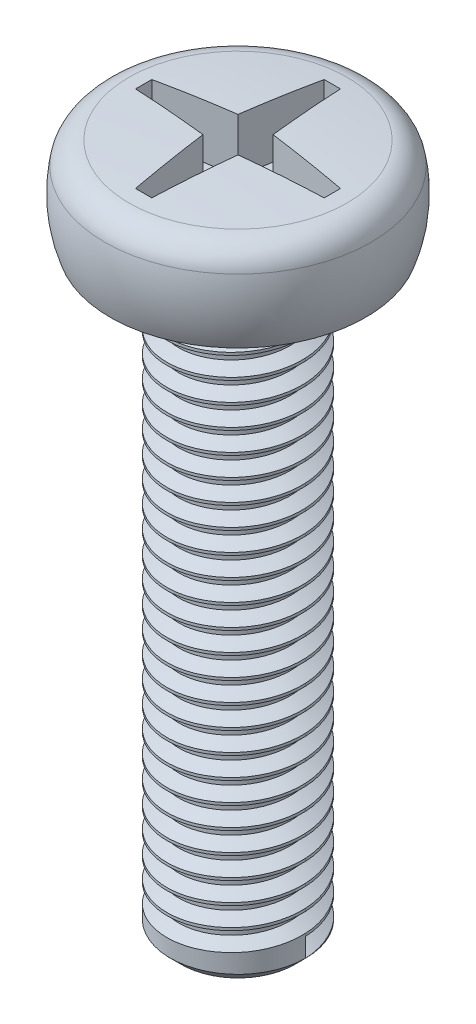
SolidWorks part; units mm, degrees
material "ASTM A36 Steel"
ref_plane "Front Plane" through (0, 0, 0) normal (0, 0, 1) x (1, 0, 0)
ref_plane "Top Plane" through (0, 0, 0) normal (0, 1, 0) x (1, 0, 0)
ref_plane "Right Plane" through (0, 0, 0) normal (1, 0, 0) x (0, 0, -1)
sketch "Sketch1" plane through (0, 0, 0) normal (0, 0, 1) x (1, 0, 0)
  line L0 (0, 3.2272) -> (0, -0.2728) construction
  line L1 (0, 3.2272) -> (5, 3.2272) construction
  line L2 (5, 3.2272) -> (5, -0.2728) construction
  line L3 (5, -0.2728) -> (0, -0.2728) construction
  line L4 (5, 1.4772) -> (0, 1.4772) construction
  line L5 (0, 2.9428) -> (4.7253, 2.9428) construction
  line L6 (4.7139, -0.2728) -> (0, -0.2728)
  line L7 (0, 3.2272) -> (0, -0.2728)
  arc A0 (4.7139, 2.9745) -> (0, 3.2272) centre (0, -40.8721) ccw
  arc A1 (4.7139, -0.2728) -> (4.7139, 2.9745) centre (0.2499, 1.3508) ccw
  point P11 (0, 1.4772)
  dimension "D1" = 3.5
  dimension "D2" = 5
revolve "Revolve1" add sketch "Sketch1" angle 360 about L7
fillet "Fillet1" radius 1 1 edges at (-4.7139, 2.9745, 0)
sketch "Sketch2" plane through (0, -0.2728, 0) normal (0, -1, 0) x (1, 0, 0)
  line L0 (0, 0) -> (0, -3.7135) construction
  line L1 (-0.3, -3.485) -> (0.3, -3.485)
  line L8 (0.3, -3.485) -> (0.6473, -0.6473)
  line L12 (-0.3, -3.485) -> (-0.6473, -0.6473)
  line L16 (-3.485, 0.3) -> (-3.485, -0.3)
  line L17 (-3.485, -0.3) -> (-0.6473, -0.6473)
  line L18 (-3.485, 0.3) -> (-0.6473, 0.6473)
  line L19 (0, 0) -> (-3.7135, 0) construction
  line L20 (0.3, 3.485) -> (-0.3, 3.485)
  line L21 (-0.3, 3.485) -> (-0.6473, 0.6473)
  line L22 (0.3, 3.485) -> (0.6473, 0.6473)
  line L23 (0, 0) -> (0, 3.7135) construction
  line L24 (3.485, -0.3) -> (3.485, 0.3)
  line L25 (3.485, 0.3) -> (0.6473, 0.6473)
  line L26 (3.485, -0.3) -> (0.6473, -0.6473)
  line L27 (0, 0) -> (3.7135, 0) construction
  point P6 (0, -3.485)
  point P15 (-3.485, 0)
  point P21 (0, 3.485)
  point P28 (3.485, 0)
  point P29 (0, 0)
  dimension "D1" = 0.3
  dimension "D2" = 4
extrude "Cut-Extrude1" cut sketch "Sketch2" along normal blind 2 from surface starting at face at (4.0261, 3.043, 0)
sketch "Sketch3" plane through (0, -0.2728, 0) normal (0, -1, 0) x (1, 0, 0)
  circle A0 centre (0, 0) radius 2.5
  dimension "D1" = 5
extrude "Boss-Extrude1" add sketch "Sketch3" along normal blind 22
chamfer "Chamfer1" distance 0.4 angle 45 1 edges at (2.5, -22.2728, 0)
thread "Thread1" pitch 0.8 start angle 0, offset 0, length 0, pitch 0.8, diameter 5
ref_plane "Plane1" through (2.5, -21.8728, 0) normal (0, 0, 1) x (1, 0, 0)
sketch "Thread Profile1" plane through (2.5, -21.8728, 0) normal (0, 0, 1) x (1, 0, 0)
  line L0 (0, 0) -> (0, 0.8) construction
  line L11 (0, 0) -> (0, 0.7)
  line L12 (0, 0.7) -> (-0.433, 0.45)
  line L13 (-0.433, 0.45) -> (-0.433, 0.25)
  line L15 (-0.433, 0.25) -> (0, 0)
  line L17 (-0.433, 0.35) -> (0, 0.35) construction
  point P2 (0, 0)
  dimension "Pitch" = 0.8
  dimension "Profile_Angle" = 60
  dimension "Profile_Land" = 0.2
  dimension "Profile_Height" = 0.433
